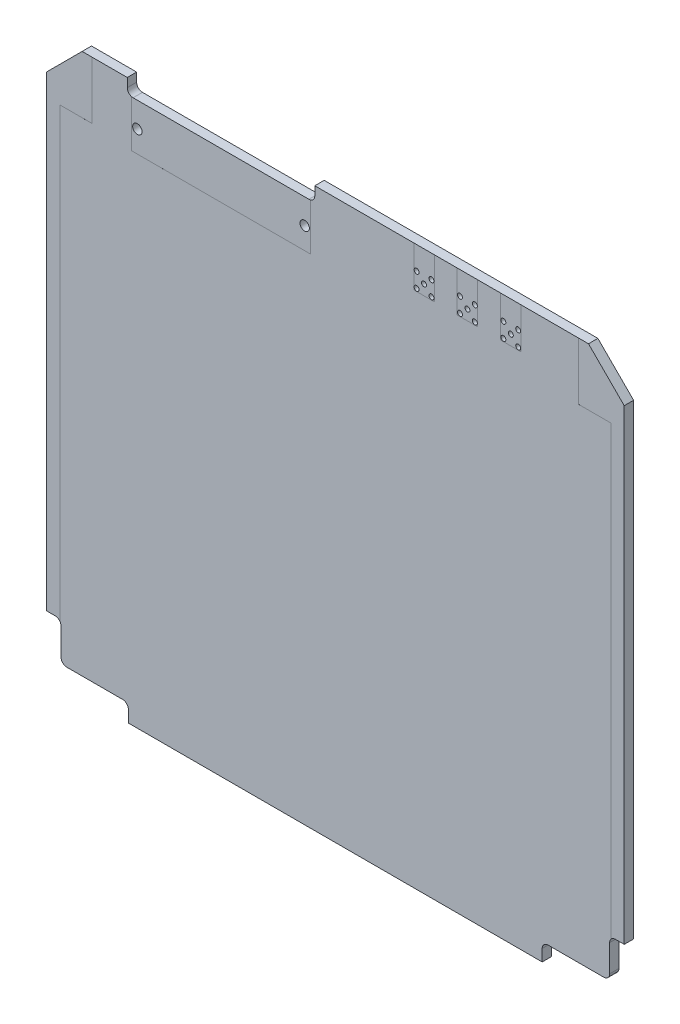
SolidWorks part; units mm, degrees
material "Oshpark board"
ref_plane "Front Plane" through (0, 0, 0) normal (0, 0, 1) x (1, 0, 0)
ref_plane "Top Plane" through (0, 0, 0) normal (0, 1, 0) x (1, 0, 0)
ref_plane "Right Plane" through (0, 0, 0) normal (1, 0, 0) x (0, 0, -1)
ref_plane "Plane4" through (0, 0, -0.0125) normal (0, 0, -1) x (-1, 0, 0)
sketch "Sketch1" plane through (0, 0, -0.0125) normal (0, 0, -1) x (-1, 0, 0)
  line L0 (35.3, -50) -> (35.3, -48)
  line L1 (36.3, -47) -> (45.8, -47)
  line L2 (46.8, -46) -> (46.8, -41.4)
  line L3 (47.8, -40.4) -> (49.3, -40.4)
  line L4 (49.3, -40.4) -> (49.3, 39.2)
  line L5 (49.3, 39.2) -> (43.2, 45.3)
  line L6 (43.2, 45.3) -> (35.5, 45.3)
  line L7 (35.5, 45.3) -> (35.5, 43.8)
  line L8 (34.5, 42.8) -> (4.5, 42.8)
  line L9 (3.5, 43.8) -> (3.5, 45.3)
  line L10 (3.5, 45.3) -> (-43.2, 45.3)
  line L11 (-43.2, 45.3) -> (-49.3, 39.2)
  line L12 (-49.3, 39.2) -> (-49.3, -40.4)
  line L13 (-49.3, -40.4) -> (-47.8, -40.4)
  line L14 (-46.8, -41.4) -> (-46.8, -46)
  line L15 (-45.8, -47) -> (-36.3, -47)
  line L16 (-35.3, -48) -> (-35.3, -50)
  line L17 (-35.3, -50) -> (35.3, -50)
  line L18 (0, -50) -> (0, 45.3) construction
  line L19 (19.5, 42.8) -> (19.5, 25.5258) construction
  line L20 (-13.87, 41.37) -> (-16.41, 38.83) construction
  line L21 (-21.27, 41.37) -> (-23.81, 38.83) construction
  line L22 (-28.67, 41.37) -> (-31.21, 38.83) construction
  arc A0 (35.3, -48) -> (36.3, -47) centre (36.3, -48) cw
  arc A1 (45.8, -47) -> (46.8, -46) centre (45.8, -46) ccw
  arc A2 (46.8, -41.4) -> (47.8, -40.4) centre (47.8, -41.4) cw
  arc A3 (35.5, 43.8) -> (34.5, 42.8) centre (34.5, 43.8) cw
  arc A4 (4.5, 42.8) -> (3.5, 43.8) centre (4.5, 43.8) cw
  arc A5 (-47.8, -40.4) -> (-46.8, -41.4) centre (-47.8, -41.4) cw
  arc A6 (-46.8, -46) -> (-45.8, -47) centre (-45.8, -46) ccw
  arc A7 (-36.3, -47) -> (-35.3, -48) centre (-36.3, -48) cw
  circle A8 centre (-21.27, 41.37) radius 0.425
  circle A9 centre (-23.81, 41.37) radius 0.425
  circle A10 centre (-22.54, 40.1) radius 0.425
  circle A11 centre (-13.87, 41.37) radius 0.425
  circle A12 centre (-23.81, 38.83) radius 0.425
  circle A13 centre (-16.41, 41.37) radius 0.425
  circle A14 centre (-15.14, 40.1) radius 0.425
  circle A15 centre (-21.27, 38.83) radius 0.425
  circle A16 centre (-28.67, 41.37) radius 0.425
  circle A17 centre (-31.21, 41.37) radius 0.425
  circle A18 centre (-16.41, 38.83) radius 0.425
  circle A19 centre (-29.94, 40.1) radius 0.425
  circle A20 centre (-31.21, 38.83) radius 0.425
  circle A21 centre (-28.67, 38.83) radius 0.425
  circle A22 centre (33.775, 38.54) radius 0.8
  circle A23 centre (5.225, 38.54) radius 0.8
  circle A24 centre (-13.87, 38.83) radius 0.425
  point P35 (-15.14, 40.1)
  dimension "D7" = 2.5
  dimension "D8" = 1.6
  dimension "D9" = 14.275
  dimension "D10" = 4.26
  dimension "D11" = 1
  dimension "D12" = 1
  dimension "D13" = 1
  dimension "D14" = 1
  dimension "D15" = 1
  dimension "D16" = 1
  dimension "D17" = 1
  dimension "D18" = 1
  dimension "D26" = 0.85
  dimension "D1" = 98.6
  dimension "D2" = 95.3
  dimension "D3" = 14
  dimension "D4" = 9.6
  dimension "D5" = 2.5
  dimension "D6" = 3
  dimension "D19" = 14
  dimension "D20" = 2.5
  dimension "D21" = 6.1
  dimension "D22" = 6.1
  dimension "D23" = 32
  dimension "D24" = 2.54
  dimension "D25" = 2.54
  dimension "D28" = 7.4
  dimension "D29" = 3.93
  dimension "D30" = 35.43
  dimension "D31" = 45
  dimension "D32" = 45
  dimension "D33" = 29.8
  dimension "D34" = 50
  dimension "D27" = 3
extrude "Boss-Extrude1" add sketch "Sketch1" against normal blind 1.6
sketch "thermalContacts_lower" plane through (0, 0, -0.0125) normal (0, 0, -1) x (-1, 0, 0)
  line L3 (47, 35.5) -> (47, -41.5)
  line L4 (41.5, 35.5) -> (41.5, 41.5)
  line L5 (41.5, 35.5) -> (47, 35.5)
  line L9 (-47, 35.5) -> (-47, -41.1726)
  line L10 (-41.5, 35.5) -> (-47, 35.5)
  line L11 (-41.5, 35.5) -> (-41.5, 42.5522)
  line L14 (-41.5, 42.5522) -> (-41.5, 47.8583)
  line L18 (41.5, 41.5) -> (41.5, 47)
  line L20 (47, -41.5) -> (59.8273, -41.5)
  line L21 (59.8273, -41.5) -> (59.8273, 47)
  line L22 (-54.1782, 47.8583) -> (-41.5, 47.8583)
  line L23 (41.5, 47) -> (59.8273, 47)
  line L24 (-54.1782, 47.8583) -> (-54.1782, -41.1726)
  line L25 (-47, -41.1726) -> (-54.1782, -41.1726)
  line L26 (43.2, 45.3) -> (35.5, 45.3) construction
  line L27 (49.3, -40.4) -> (49.3, 39.2) construction
  line L28 (3.5, 45.3) -> (-43.2, 45.3) construction
  line L29 (-49.3, 39.2) -> (-49.3, -40.4) construction
  point P10 (-41.5, 42.5522)
  point P24 (-43.5139, 47.5309)
  dimension "D1" = 9.8
  dimension "D2" = 7.8
  dimension "D3" = 2.3
  dimension "D4" = 9.8
  dimension "D5" = 7.8
  dimension "D6" = 2.3
sketch "thermalContacts_upper" plane through (0, 0, 1.5875) normal (0, 0, 1) x (1, 0, 0)
  line L3 (-47, 35.5) -> (-47, -41.5)
  line L4 (-41.5, 35.5) -> (-41.5, 41.5)
  line L5 (-41.5, 35.5) -> (-47, 35.5)
  line L9 (47, 35.5) -> (47, -41.5)
  line L10 (41.5, 35.5) -> (47, 35.5)
  line L11 (41.5, 35.5) -> (41.5, 41.5)
  line L14 (41.5, 41.5) -> (41.5, 47)
  line L15 (41.5, 41.5) -> (49.5, 41.5) construction
  line L18 (-41.5, 41.5) -> (-41.5, 47)
  line L19 (-41.5, 41.5) -> (-49.5, 41.5) construction
  line L20 (47, -41.5) -> (59.8273, -41.5)
  line L21 (59.8273, -41.5) -> (59.8273, 47)
  line L22 (59.8273, 47) -> (41.5, 47)
  line L23 (-41.5, 47) -> (-56.1922, 47)
  line L24 (-56.1922, 47) -> (-56.1922, -41.5)
  line L25 (-56.1922, -41.5) -> (-47, -41.5)
extrude "Cut-Extrude1" cut sketch "thermalContacts_lower" against normal blind 0.0001
extrude "Cut-Extrude2" cut sketch "thermalContacts_upper" against normal blind 0.0001
sketch "partFootprints" plane through (0, 0, 1.5875) normal (0, 0, 1) x (1, 0, 0)
  line L0 (-34.74, 34.84) -> (-34.74, 42.8292)
  line L1 (-4.26, 34.84) -> (-34.74, 34.84)
  line L2 (-41.5, 45.3) -> (-35.5, 45.3) construction
  line L3 (-36.1132, 45.3) -> (-39.5054, 45.3) construction
  line L4 (-4.26, 34.84) -> (-4.26, 42.8292)
  line L5 (-49.3, -40.4) -> (-49.3, 39.2) construction
  line L6 (13.39, 45.3) -> (13.39, 38.35)
  line L7 (13.39, 38.35) -> (16.89, 38.35)
  line L8 (16.89, 38.35) -> (16.89, 45.3)
  line L9 (16.89, 45.3) -> (13.39, 45.3)
  line L10 (20.79, 45.3) -> (20.79, 38.35)
  line L11 (20.79, 38.35) -> (24.29, 38.35)
  line L12 (24.29, 38.35) -> (24.29, 45.3)
  line L13 (24.29, 45.3) -> (20.79, 45.3)
  line L14 (28.19, 45.3) -> (28.19, 38.35)
  line L15 (28.19, 38.35) -> (31.69, 38.35)
  line L16 (31.69, 38.35) -> (31.69, 45.3)
  line L17 (31.69, 45.3) -> (28.19, 45.3)
  line L18 (49.3, -40.4) -> (49.3, 39.2) construction
  line L20 (-34.74, 42.8292) -> (-4.26, 42.8292)
  line L21 (-3.5, 45.3) -> (41.5, 45.3) construction
  line L22 (14.12, 38.35) -> (15.8235, 38.35) construction
  line L25 (13.39, 42.2411) -> (13.39, 38.35) construction
  line L26 (16.89, 41.85) -> (16.89, 38.35) construction
  arc A0 (-35.5, 43.8) -> (-34.5, 42.8) centre (-34.5, 43.8) ccw construction
  arc A1 (-4.5, 42.8) -> (-3.5, 43.8) centre (-4.5, 43.8) ccw construction
  point P17 (0, 0)
  point P18 (0, 0)
  point P34 (0, 0)
  point P35 (13.39, 36.9932)
  point P39 (13.39, 42.2411)
  point P40 (15.8235, 38.405)
  point P41 (13.39, 38.35)
  point P42 (0, 0)
  point P43 (0, 0)
  point P44 (0, 0)
  dimension "D1" = 10.46
  dimension "D2" = 14.56
  dimension "D3" = 30.48
  dimension "D4" = 6.95
  dimension "D5" = 17.61
  dimension "D7" = 7.4
  dimension "D8" = 3.5
  dimension "D6" = 3
extrude "Cut-Extrude3" cut sketch "partFootprints" against normal blind 0.0001
